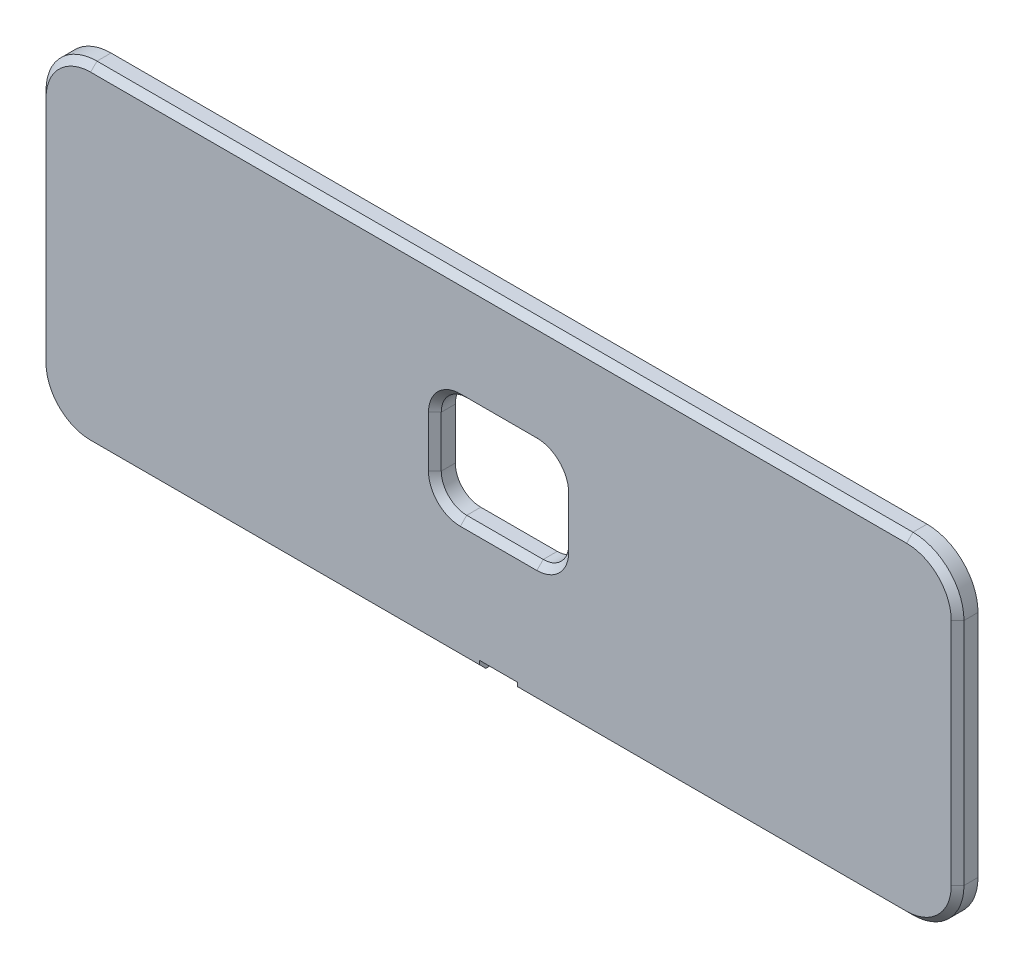
SolidWorks part; units mm, degrees
ref_plane "Front Plane" through (0, 0, 0) normal (0, 0, 1) x (1, 0, 0)
ref_plane "Top Plane" through (0, 0, 0) normal (0, 1, 0) x (1, 0, 0)
ref_plane "Right Plane" through (0, 0, 0) normal (1, 0, 0) x (0, 0, -1)
sketch "Sketch1" plane through (0, 0, 0) normal (0, 0, 1) x (1, 0, 0)
  line L0 (-32, 8.6) -> (32, 8.6)
  line L1 (36, 12.6) -> (36, 30.6)
  line L2 (32, 34.6) -> (-32, 34.6)
  line L3 (-36, 30.6) -> (-36, 12.6)
  arc A0 (-36, 12.6) -> (-32, 8.6) centre (-32, 12.6) ccw
  arc A1 (32, 8.6) -> (36, 12.6) centre (32, 12.6) ccw
  arc A2 (36, 30.6) -> (32, 34.6) centre (32, 30.6) ccw
  arc A3 (-32, 34.6) -> (-36, 30.6) centre (-32, 30.6) ccw
extrude "Boss-Extrude1" add sketch "Sketch1" along normal blind 1.6 from offset 78.4
chamfer "Chamfer1" distance 0.5 angle 45 8 edges at (0, 8.6, 80) (34.8284, 9.7716, 80) (-34.8284, 9.7716, 80) (36, 21.6, 80) (-36, 21.6, 80) (34.8284, 33.4284, 80) (-34.8284, 33.4284, 80) (0, 34.6, 80)
sketch "Sketch2" plane through (0, 0, 0) normal (0, 0, 1) x (1, 0, 0)
  line L0 (-3, 18.25) -> (3, 18.25)
  line L1 (5, 20.25) -> (5, 24.25)
  line L2 (3, 26.25) -> (-3, 26.25)
  line L3 (-5, 24.25) -> (-5, 20.25)
  arc A0 (-5, 20.25) -> (-3, 18.25) centre (-3, 20.25) ccw
  arc A1 (3, 18.25) -> (5, 20.25) centre (3, 20.25) ccw
  arc A2 (5, 24.25) -> (3, 26.25) centre (3, 24.25) ccw
  arc A3 (-3, 26.25) -> (-5, 24.25) centre (-3, 24.25) ccw
extrude "Boss-Extrude2" add sketch "Sketch2" along normal blind 3 from offset 78 separate body
combine bodies "Combine1" operation type subtract main body 101 bodies to subtract 102
chamfer "Chamfer2" distance 0.5 angle 45 8 edges at (0, 18.25, 80) (-4.4142, 18.8358, 80) (4.4142, 18.8358, 80) (-5, 22.25, 80) (5, 22.25, 80) (-4.4142, 25.6642, 80) (4.4142, 25.6642, 80) (0, 26.25, 80)
sketch "Sketch3" plane through (0, 0, 0) normal (0, 0, 1) x (1, 0, 0)
  line L1 (-1.5, 8.5) -> (1.5, 8.5)
  line L2 (-1.5, 8.5) -> (-1.5, 9.4)
  line L3 (-1.5, 9.4) -> (1.5, 9.4)
  line L4 (1.5, 8.5) -> (1.5, 9.4)
extrude "Boss-Extrude3" add sketch "Sketch3" along normal blind 0.9 from offset 79.2 separate body
combine bodies "Combine2" operation type subtract main body 103 bodies to subtract 104
sketch "Sketch4" plane through (0, 0, 0) normal (1, 0, 0) x (0, 0, -1)
  line L0 (-78.41, 12) -> (-74.6, 12)
  line L1 (-74.6, 12) -> (-74.6, 12.8)
  line L2 (-74.6, 12.8) -> (-74.9, 13.1)
  line L3 (-74.9, 13.1) -> (-75.2, 13.1)
  line L4 (-75.2, 13.1) -> (-75.2, 12.8)
  line L5 (-75.2, 12.8) -> (-78.41, 12.8)
  line L6 (-78.41, 12.8) -> (-78.41, 12)
extrude "Boss-Extrude4" add sketch "Sketch4" along normal blind 4 from offset 32 offset against normal yes
sketch "Sketch5" plane through (0, 0, 0) normal (1, 0, 0) x (0, 0, -1)
  line L0 (-78.41, 12) -> (-74.6, 12)
  line L1 (-74.6, 12) -> (-74.6, 12.8)
  line L2 (-74.6, 12.8) -> (-74.9, 13.1)
  line L3 (-74.9, 13.1) -> (-75.2, 13.1)
  line L4 (-75.2, 13.1) -> (-75.2, 12.8)
  line L5 (-75.2, 12.8) -> (-78.41, 12.8)
  line L6 (-78.41, 12.8) -> (-78.41, 12)
extrude "Boss-Extrude5" add sketch "Sketch5" along normal blind 4 from offset 28
